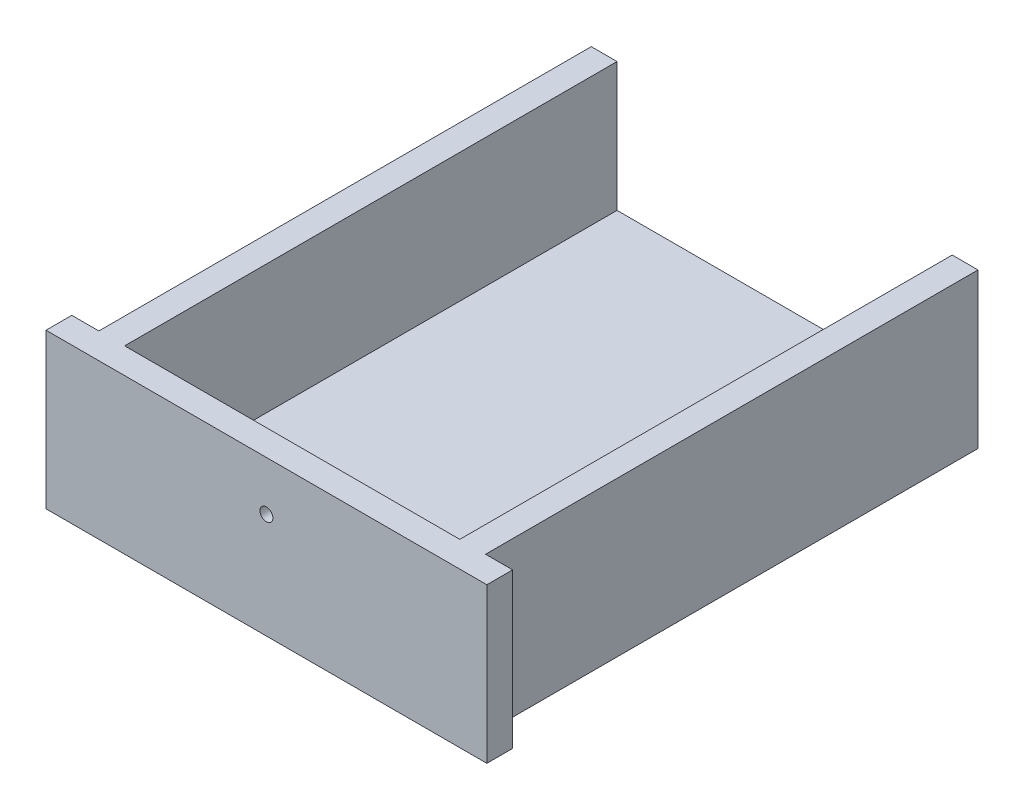
SolidWorks part; units mm, degrees
ref_plane "Front Plane" through (0, 0, 0) normal (0, 0, 1) x (1, 0, 0)
ref_plane "Top Plane" through (0, 0, 0) normal (0, 1, 0) x (1, 0, 0)
ref_plane "Right Plane" through (0, 0, 0) normal (1, 0, 0) x (0, 0, -1)
sketch "Sketch1" plane through (0, -22.3524, -0.0002) normal (0, 1, 0) x (1, 0, 0)
  line L6 (80.2805, 6.867) -> (80.2805, 25.967)
  line L7 (80.2805, 6.867) -> (80.2805, 25.967)
  line L14 (80.2805, 25.967) -> (64.7805, 25.967)
  line L15 (80.2805, 25.967) -> (64.7805, 25.967)
  line L16 (64.7805, 25.967) -> (64.7805, 5.967)
  line L17 (64.7805, 25.967) -> (64.7805, 5.967)
  line L26 (148.6829, 25.967) -> (133.1805, 25.967)
  line L27 (148.6829, 25.967) -> (133.1805, 25.967)
  line L28 (133.1805, 25.967) -> (133.1805, 5.967)
  line L29 (133.1805, 25.967) -> (133.1805, 5.967)
  line L75 (116.0805, 6.867) -> (114.4805, 6.867)
  line L76 (116.0805, 6.867) -> (114.4805, 6.867)
  line L77 (131.5805, 5.967) -> (131.5805, 25.967)
  line L78 (131.5805, 5.967) -> (131.5805, 25.967)
  line L79 (64.7805, 5.967) -> (62.5853, 5.967)
  line L80 (64.7805, 5.967) -> (62.5853, 5.967)
  line L81 (148.6829, 5.967) -> (148.6829, 25.967)
  line L82 (148.6829, 5.967) -> (148.6829, 25.967)
  line L83 (131.5805, 25.967) -> (116.0805, 25.967)
  line L84 (131.5805, 25.967) -> (116.0805, 25.967)
  line L85 (116.0805, 25.967) -> (116.0805, 6.867)
  line L86 (116.0805, 25.967) -> (116.0805, 6.867)
  line L87 (98.9805, 6.867) -> (97.3805, 6.867)
  line L88 (98.9805, 6.867) -> (97.3805, 6.867)
  line L89 (114.4805, 6.867) -> (114.4805, 25.967)
  line L90 (114.4805, 6.867) -> (114.4805, 25.967)
  line L91 (114.4805, 25.967) -> (98.9805, 25.967)
  line L92 (114.4805, 25.967) -> (98.9805, 25.967)
  line L93 (98.9805, 25.967) -> (98.9805, 6.867)
  line L94 (98.9805, 25.967) -> (98.9805, 6.867)
  line L95 (81.8805, 6.867) -> (80.2805, 6.867)
  line L96 (81.8805, 6.867) -> (80.2805, 6.867)
  line L97 (97.3805, 6.867) -> (97.3805, 25.967)
  line L98 (97.3805, 6.867) -> (97.3805, 25.967)
  line L99 (97.3805, 25.967) -> (81.8805, 25.967)
  line L100 (97.3805, 25.967) -> (81.8805, 25.967)
  line L101 (81.8805, 25.967) -> (81.8805, 6.867)
  line L102 (81.8805, 25.967) -> (81.8805, 6.867)
  line L111 (151.0746, 5.967) -> (148.6829, 5.967)
  line L112 (151.0746, 5.967) -> (148.6829, 5.967)
  line L149 (133.1805, 5.967) -> (131.5805, 5.967)
  line L150 (133.1805, 5.967) -> (131.5805, 5.967)
  arc A1 (62.5853, 5.967) -> (62.6384, 5.8755) centre (75.6644, 13.4963) ccw
  arc A2 (62.5853, 5.967) -> (62.6384, 5.8755) centre (75.6644, 13.4963) ccw
  spline S3 degree 3 poles (2721.6631, 1389.8264) (-2734.3118, -1200.7766) (2906.8002, 1122.7786) (-2704.8314, -1148.9599) knots -34.159239 -34.159239 -34.159239 -34.159239 37.482662 37.482662 37.482662 37.482662 only from (63.2069, 4.9792) to (64.6069, 3.1717)
  spline S4 degree 3 poles (775.875, -2910.9198) (78.3925, 144.0456) (40.7797, 26.5802) (66.0259, 1.6806) (66.407, 1.3399) (67.5936, 0.3721) (68.44, -0.2041) (70.2044, -1.2669) (71.1081, -1.7488) (72.9497, -2.6116) (73.8899, -2.9905) (75.8005, -3.6662) (76.7705, -3.9643) (78.7232, -4.5262) (79.7054, -4.7912) (81.678, -5.2989) (82.6694, -5.5379) (84.658, -5.9748) (85.6562, -6.1718) (87.6567, -6.5442) (88.6588, -6.7199) (90.6645, -7.064) (91.6682, -7.2318) (94.6817, -7.721) (96.6958, -8.0266) (99.7213, -8.4164) (100.7307, -8.5334) (102.7546, -8.704) (103.7688, -8.7591) (105.8015, -8.8138) (106.8197, -8.8174) (108.859, -8.7878) (109.8772, -8.7557) (111.9061, -8.6254) (112.9167, -8.524) (114.9339, -8.2838) (115.9406, -8.1453) (118.9579, -7.7054) (120.9662, -7.374) (123.9704, -6.8548) (124.9707, -6.6779) (126.9684, -6.3136) (127.9654, -6.125) (129.9492, -5.7108) (130.9357, -5.4844) (132.8984, -4.9951) (133.8758, -4.7363) (135.824, -4.195) (136.7954, -3.9144) (138.7201, -3.289) (139.6729, -2.9424) (141.0799, -2.3428) (141.5456, -2.1311) (142.472, -1.69) (142.9335, -1.463) (143.8467, -0.9745) (144.3011, -0.7093) (145.165, -0.13) (145.5785, 0.1817) (146.1902, 0.6595) (146.3927, 0.8204) (146.7979, 1.1421) (147.0003, 1.3032) (167.6067, 18.0823) (168.7332, 57.7618) (-1715.1502, 2352.4589) knots -0.949034 -0.949034 -0.949034 -0.949034 0.115071 0.115071 0.130696 0.130696 0.161946 0.161946 0.193196 0.193196 0.224446 0.224446 0.255696 0.255696 0.286946 0.286946 0.318196 0.318196 0.349446 0.349446 0.380696 0.380696 0.411946 0.411946 0.474446 0.474446 0.505696 0.505696 0.536946 0.536946 0.568196 0.568196 0.599446 0.599446 0.630696 0.630696 0.661946 0.661946 0.724446 0.724446 0.755696 0.755696 0.786946 0.786946 0.818196 0.818196 0.849446 0.849446 0.880696 0.880696 0.911946 0.911946 0.927571 0.927571 0.943196 0.943196 0.958821 0.958821 0.974446 0.974446 0.982259 0.982259 0.990071 0.990071 1.785034 1.785034 1.785034 1.785034 only from (64.6069, 3.1717) to (147.9528, 2.1042)
  spline S6 degree 3 poles (63.2069, 4.9792) (63.6398, 4.3447) (64.1129, 3.7449) (64.6069, 3.1717) knots 0 0 0 0 0.685452 0.685452 0.685452 0.685452 construction
  spline S7 degree 3 poles (64.6069, 3.1717) (64.9434, 2.7816) (65.2953, 2.4012) (66.0259, 1.6806) (66.407, 1.3399) (67.5936, 0.3721) (68.44, -0.2041) (70.2044, -1.2669) (71.1081, -1.7488) (72.9497, -2.6116) (73.8899, -2.9905) (75.8005, -3.6662) (76.7705, -3.9643) (78.7232, -4.5262) (79.7054, -4.7912) (81.678, -5.2989) (82.6694, -5.5379) (84.658, -5.9748) (85.6562, -6.1718) (87.6567, -6.5442) (88.6588, -6.7199) (90.6645, -7.064) (91.6682, -7.2318) (94.6817, -7.721) (96.6958, -8.0266) (99.7213, -8.4164) (100.7307, -8.5334) (102.7546, -8.704) (103.7688, -8.7591) (105.8015, -8.8138) (106.8197, -8.8174) (108.859, -8.7878) (109.8772, -8.7557) (111.9061, -8.6254) (112.9167, -8.524) (114.9339, -8.2838) (115.9406, -8.1453) (118.9579, -7.7054) (120.9662, -7.374) (123.9704, -6.8548) (124.9707, -6.6779) (126.9684, -6.3136) (127.9654, -6.125) (129.9492, -5.7108) (130.9357, -5.4844) (132.8984, -4.9951) (133.8758, -4.7363) (135.824, -4.195) (136.7954, -3.9144) (138.7201, -3.289) (139.6729, -2.9424) (141.0799, -2.3428) (141.5456, -2.1311) (142.472, -1.69) (142.9335, -1.463) (143.8467, -0.9745) (144.3011, -0.7093) (145.165, -0.13) (145.5785, 0.1817) (146.1902, 0.6595) (146.3927, 0.8204) (146.7979, 1.1421) (147.0003, 1.3032) (147.4557, 1.674) (147.7076, 1.8851) (147.9528, 2.1042) knots 0.099446 0.099446 0.099446 0.099446 0.115071 0.115071 0.130696 0.130696 0.161946 0.161946 0.193196 0.193196 0.224446 0.224446 0.255696 0.255696 0.286946 0.286946 0.318196 0.318196 0.349446 0.349446 0.380696 0.380696 0.411946 0.411946 0.474446 0.474446 0.505696 0.505696 0.536946 0.536946 0.568196 0.568196 0.599446 0.599446 0.630696 0.630696 0.661946 0.661946 0.724446 0.724446 0.755696 0.755696 0.786946 0.786946 0.818196 0.818196 0.849446 0.849446 0.880696 0.880696 0.911946 0.911946 0.927571 0.927571 0.943196 0.943196 0.958821 0.958821 0.974446 0.974446 0.982259 0.982259 0.990071 0.990071 1 1 1 1 construction
  spline S16 degree 3 poles (2008.2711, -2350.5373) (48.4338, 36.6769) (128.6772, -16.6361) (148.7396, 2.8512) (149.0893, 3.2405) (149.7556, 4.0536) (150.0701, 4.4713) (170.0716, 32.7524) (120.2035, 102.4679) (-2365.2062, 1637.6818) knots -0.771632 -0.771632 -0.771632 -0.771632 0.055384 0.055384 0.071009 0.071009 0.086634 0.086634 1.108808 1.108808 1.108808 1.108808 only from (147.9528, 2.1042) to (151.0746, 5.967)
  spline S17 degree 3 poles (147.9528, 2.1042) (148.0935, 2.2299) (148.232, 2.3582) (148.7396, 2.8512) (149.0893, 3.2405) (149.7556, 4.0536) (150.0701, 4.4713) (150.6182, 5.2462) (150.8542, 5.602) (151.0746, 5.967) knots 0.049688 0.049688 0.049688 0.049688 0.055384 0.055384 0.071009 0.071009 0.086634 0.086634 0.099446 0.099446 0.099446 0.099446
  spline S46 degree 3 poles (2721.6922, 1389.8402) (-2734.5094, -1200.8691) (2907.1772, 1122.9338) (-2705.379, -1149.1817) knots -33.159366 -33.159366 -33.159366 -33.159366 38.484993 38.484993 38.484993 38.484993 only from (62.6384, 5.8755) to (63.2069, 4.9792)
  spline S47 degree 3 poles (62.6384, 5.8755) (62.8181, 5.5689) (63.0083, 5.2704) (63.2069, 4.9792) knots 0.685452 0.685452 0.685452 0.685452 1 1 1 1
  dimension "D1" = 0
sketch "Sketch3" plane through (0, 0.0002, -25.967) normal (0, 0, 1) x (1, 0, 0)
  line L0 (98.9805, -22.3524) -> (98.9806, 145.4576) construction
  line L2 (99.2306, 46.7197) -> (99.2306, 45.7197)
  line L3 (99.2306, 45.7197) -> (114.2306, 45.7197)
  line L4 (114.2306, 46.7197) -> (114.2306, 45.7197)
  line L5 (114.4805, -22.3525) -> (114.4806, 145.4575) construction
  line L6 (100.2306, 46.7197) -> (113.2306, 46.7197)
  line L10 (99.2306, 46.7197) -> (99.2306, 51.7197)
  line L11 (99.2306, 51.7197) -> (100.2306, 51.7197)
  line L12 (100.2306, 46.7197) -> (100.2306, 51.7197)
  line L14 (114.2306, 46.7197) -> (114.2306, 51.7197)
  line L15 (114.2306, 51.7197) -> (113.2306, 51.7197)
  line L16 (113.2306, 46.7197) -> (113.2306, 51.7197)
  dimension "D1" = 15
  dimension "D2" = 0.25
  dimension "D3" = 0.25
  dimension "D5" = 1
  dimension "D6" = 5
extrude "Boss-Extrude1" add sketch "Sketch3" along normal up to surface (19.1 mm away)
sketch "Sketch4" plane through (0, 0.0001, -6.867) normal (0, 0, 1) x (1, 0, 0)
  line L0 (97.3805, -22.3524) -> (97.3806, 145.4576) construction
  line L1 (98.1806, 51.7197) -> (115.2806, 51.7197)
  line L2 (98.1806, 51.7197) -> (98.1806, 45.7197)
  line L3 (98.1806, 45.7197) -> (115.2806, 45.7197)
  line L4 (115.2806, 51.7197) -> (115.2806, 45.7197)
  line L5 (98.9805, -22.3524) -> (98.9806, 145.4576) construction
  line L6 (97.3806, 37.2586) -> (98.9806, 37.2586) construction
  line L7 (113.2306, 51.7197) -> (114.2306, 51.7197) construction
  line L9 (98.1806, 37.2586) -> (98.1806, 50.3435) construction
  line L10 (114.4806, 37.2586) -> (116.0806, 37.2586) construction
  line L13 (115.2806, 37.2586) -> (115.2806, 50.5667) construction
  line L14 (114.4805, -22.3525) -> (114.4806, 145.4575) construction
  line L15 (116.0805, -22.3525) -> (116.0806, 145.4575) construction
  line L16 (114.2306, 45.7197) -> (99.2306, 45.7197) construction
extrude "Boss-Extrude2" add sketch "Sketch4" along normal blind 1
sketch "Sketch6" plane through (0, 0, -5.867) normal (0, 0, 1) x (1, 0, 0)
  line L0 (98.1806, 48.7197) -> (115.2806, 48.7197) construction
  line L1 (98.1806, 51.7197) -> (98.1806, 45.7197) construction
  line L2 (115.2806, 45.7197) -> (115.2806, 51.7197) construction
  line L3 (106.7306, 51.7197) -> (106.7306, 45.7197) construction
  line L4 (115.2806, 51.7197) -> (98.1806, 51.7197) construction
  line L5 (98.1806, 45.7197) -> (115.2806, 45.7197) construction
  point P0 (106.7306, 49.8079)
hole_wizard "Ø1.0mm Dowel Hole1" positions "Sketch7" profile "Sketch8" hole size "Ø1.0" standard "AS" end condition up to next
sketch "Sketch7" plane through (0, 0, -5.867) normal (0, 0, 1) x (1, 0, 0)
  point P0 (106.7306, 49.8079)
sketch "Sketch8" plane through (106.7306, 49.8079, -5.8666) normal (1, 0, 0) x (0, -1, 0)
  line L0 (0, 0) -> (0, 1)
  line L1 (0, 1) -> (0.25, 1)
  line L2 (0.25, 1) -> (0.25, 0)
  line L5 (0.25, 0) -> (0, 0)
  line L11 (0, -6.35) -> (0, 107.95) construction
  dimension "Thru Hole Dia." = 0.5
  dimension "Thru Hole Depth" = 1
